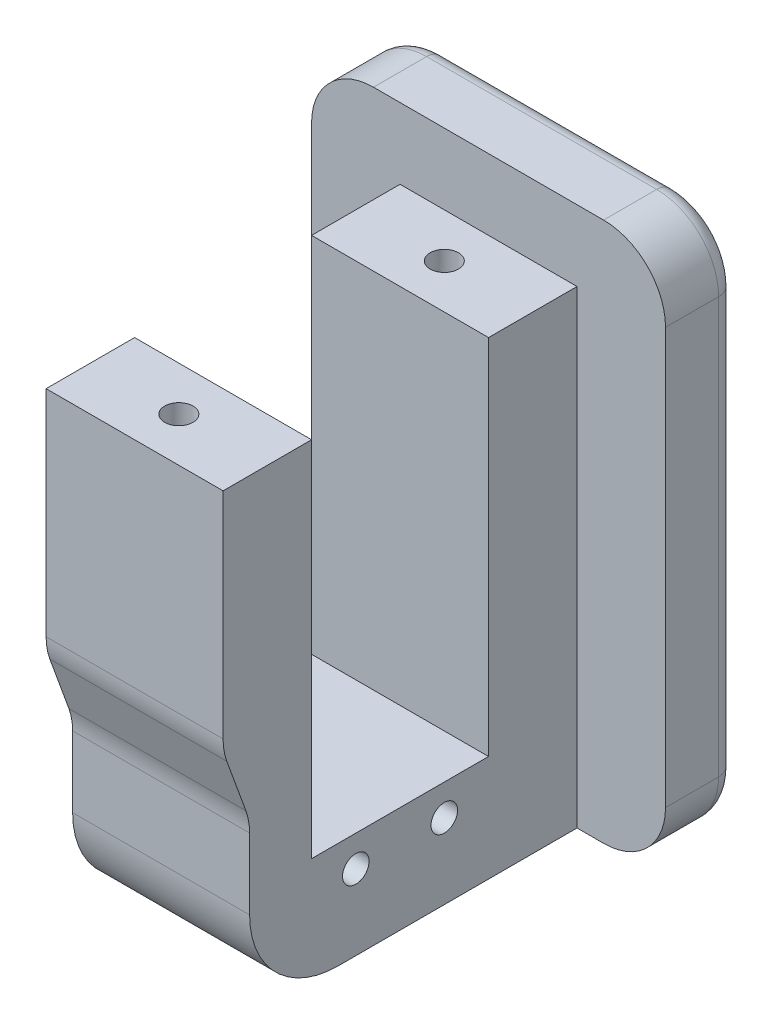
SolidWorks part; units mm, degrees
ref_plane "Front Plane" through (0, 0, 0) normal (0, 0, 1) x (1, 0, 0)
ref_plane "Top Plane" through (0, 0, 0) normal (0, 1, 0) x (1, 0, 0)
ref_plane "Right Plane" through (0, 0, 0) normal (1, 0, 0) x (0, 0, -1)
sketch "Sketch3" plane through (0, 0, 30) normal (0, 0, -1) x (-1, 0, 0)
  line L0 (95, 33.2573) -> (65, 33.2573) construction
  line L15 (80, 53.2573) -> (80, 33.2573) construction
  line L20 (55, 53.2573) -> (105, 53.2573)
  line L29 (55, -26.7427) -> (105, -26.7427)
  line L31 (110, -21.7427) -> (110, 48.2573)
  line L33 (50, -21.7427) -> (50, 48.2573)
  arc A17 (50, 48.2573) -> (55, 53.2573) centre (55, 48.2573) cw
  arc A18 (110, 48.2573) -> (105, 53.2573) centre (105, 48.2573) ccw
  arc A21 (50, -21.7427) -> (55, -26.7427) centre (55, -21.7427) ccw
  arc A22 (110, -21.7427) -> (105, -26.7427) centre (105, -21.7427) cw
  dimension "D1" = 5
extrude "Boss-Extrude1" add sketch "Sketch3" along normal blind 8
ref_plane "Plane1" through (-80, 0, 0) normal (-1, 0, 0) x (0, 0, 1)
sketch "Sketch8" plane through (0, 0, 22) normal (0, 0, -1) x (-1, 0, 0)
  line L0 (50, 13.2573) -> (110, 13.2573) construction
  line L1 (50, 48.2573) -> (50, -21.7427) construction
  line L2 (110, -21.7427) -> (110, 48.2573) construction
  line L3 (80, 13.2573) -> (80, -26.7427) construction
  line L4 (55, -26.7427) -> (105, -26.7427) construction
  line L5 (78.25, 15.3786) -> (78.25, 11.136)
  line L6 (81.75, 15.3786) -> (81.75, 11.136)
  arc A0 (78.25, 11.136) -> (81.75, 11.136) centre (80, 13.2573) ccw
  arc A1 (81.75, 15.3786) -> (78.25, 15.3786) centre (80, 13.2573) ccw
extrude "Cut-Extrude3" cut sketch "Sketch8" against normal blind 3
sketch "Sketch10" plane through (0, 0, 22) normal (0, 0, -1) x (-1, 0, 0)
  line L0 (50, 13.2573) -> (110, 13.2573) construction
  line L1 (50, 48.2573) -> (50, -21.7427) construction
  line L2 (110, -21.7427) -> (110, 48.2573) construction
  line L3 (80, 13.2573) -> (80, -26.7427) construction
  line L4 (55, -26.7427) -> (105, -26.7427) construction
  line L7 (81.75, 11.136) -> (81.75, 15.3786)
  line L8 (78.25, 15.3786) -> (78.25, 11.136)
  line L9 (81.75, 11.136) -> (81.75, 15.3786)
  line L10 (78.25, 15.3786) -> (78.25, 11.136)
  circle A3 centre (80, 13.2573) radius 9.75
  arc A5 (78.25, 11.136) -> (81.75, 11.136) centre (80, 13.2573) ccw
  arc A6 (81.75, 15.3786) -> (78.25, 15.3786) centre (80, 13.2573) ccw
  arc A7 (78.25, 11.136) -> (81.75, 11.136) centre (80, 13.2573) ccw
  arc A8 (81.75, 15.3786) -> (78.25, 15.3786) centre (80, 13.2573) ccw
  dimension "D1" = 0
extrude "Boss-Extrude4" add sketch "Sketch10" along normal blind 9
sketch "Sketch12" plane through (-80, 0, 0) normal (-1, 0, 0) x (0, 0, 1)
  line L0 (30, -19.2427) -> (30, 33.7573)
  line L2 (30, -21.7427) -> (30, 48.2573) construction
  line L21 (40, 33.7573) -> (40, -7.2427)
  line L22 (40, -7.2427) -> (60, -7.2427)
  line L24 (67.0011, -19.2427) -> (30, -19.2427)
  line L25 (40, 0.0073) -> (40, 26.5073) construction
  line L27 (60, -6.9927) -> (40, -6.9927) construction
  line L35 (60, 39.4573) -> (60, 33.5073) construction
  line L36 (60, 33.7573) -> (60, -7.2427)
  line L40 (60, 33.7573) -> (70, 33.7573)
  line L41 (40, 33.7573) -> (30, 33.7573)
  line L42 (70, 33.7573) -> (70, 8.2394)
  line L43 (70, 8.2394) -> (67.0011, 0)
  line L44 (67.0011, 0) -> (67.0011, -19.2427)
  dimension "D1" = 0
  dimension "D2" = 10
  dimension "D3" = 0.25
  dimension "D4" = 160
extrude "Boss-Extrude5" add sketch "Sketch12" along normal mid plane 20
sketch "Sketch13" plane through (-70, 0, 0) normal (1, 0, 0) x (0, 0, -1)
  circle A0 centre (-55, -10.7427) radius 1.5
  circle A1 centre (-45, -10.7427) radius 1.5
  circle A2 centre (-55, 37.2573) radius 1.5
  circle A3 centre (-45, 37.2573) radius 1.5
extrude "Cut-Extrude4" cut sketch "Sketch13" against normal blind 10
sketch "Sketch14" plane through (0, 0, 22) normal (0, 0, -1) x (-1, 0, 0)
  circle A0 centre (80, 13.2573) radius 12
extrude "Boss-Extrude6" add sketch "Sketch14" along normal blind 1
fillet "Fillet4" radius 10 1 edges at (-80, -19.2427, 67.0011)
fillet "Fillet5" radius 7 2 edges at (-80, 8.2394, 70) (-80, 0, 67.0011)
sketch "Sketch15" plane through (0, 0, 30) normal (0, 0, 1) x (1, 0, 0)
  line L1 (-100, -19.2427) -> (-60, -19.2427)
  line L3 (-100, 41.7573) -> (-60, 41.7573)
  line L7 (-60, 41.7573) -> (-60, -19.2427)
  line L8 (-80, 33.7573) -> (-80, 14.8628) construction
  line L9 (-90, 33.7573) -> (-70, 33.7573) construction
  line L10 (-100, 41.7573) -> (-100, -19.2427)
  dimension "D1" = 20
  dimension "D2" = 20
extrude "Cut-Extrude5" cut sketch "Sketch15" against normal through all flip side to cut
fillet "Fillet6" radius 7 4 edges at (-60, -19.2427, 26) (-100, -19.2427, 26) (-100, 41.7573, 26) (-60, 41.7573, 26)
sketch "Sketch16" plane through (0, 33.7573, 0) normal (0, 1, 0) x (1, 0, 0)
  circle A0 centre (-80, -65) radius 1.6
  circle A1 centre (-80, -35) radius 1.6
extrude "Cut-Extrude6" cut sketch "Sketch16" against normal blind 15
fillet "Fillet7" radius 2 8 edges at (-62.0503, 39.707, 22) (-80, 41.7573, 22) (-97.9497, 39.707, 22) (-100, 11.2573, 22) (-97.9497, -17.1925, 22) (-80, -19.2427, 22) (-62.0503, -17.1925, 22) (-60, 11.2573, 22)
